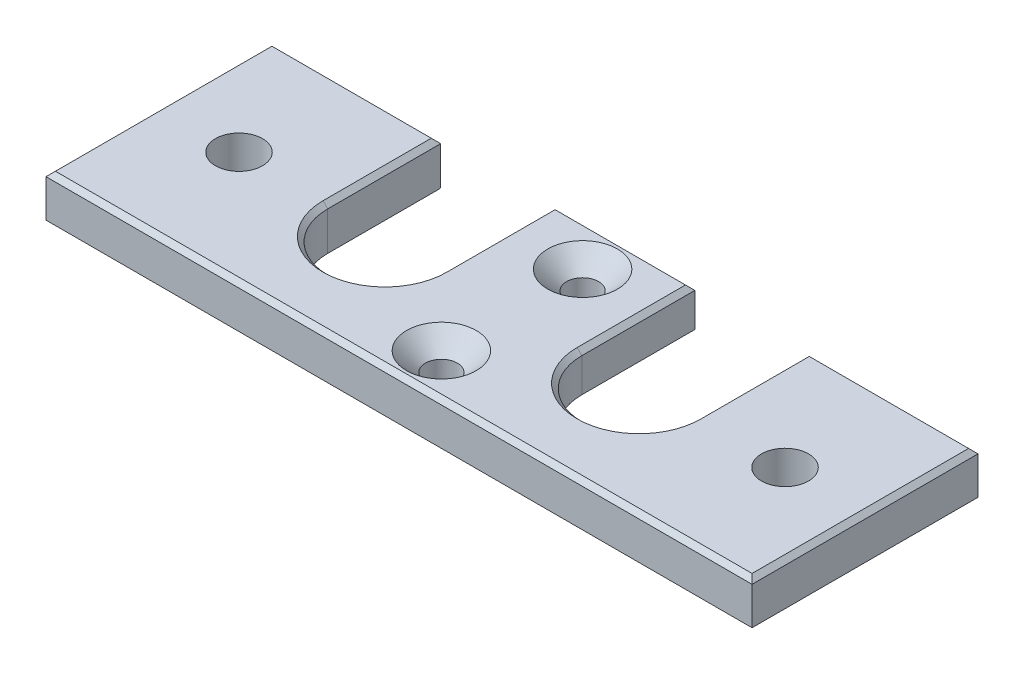
SolidWorks part; units mm, degrees
ref_plane "Front Plane" through (0, 0, 0) normal (0, 0, 1) x (1, 0, 0)
ref_plane "Top Plane" through (0, 0, 0) normal (0, 1, 0) x (1, 0, 0)
ref_plane "Right Plane" through (0, 0, 0) normal (1, 0, 0) x (0, 0, -1)
sketch "Sketch1" plane through (0, 0, 0) normal (0, 1, 0) x (1, 0, 0)
  line L0 (0, 0) -> (0, 50000) construction
  line L1 (37.5, -12) -> (-37.5, -12)
  line L2 (37.5, -12) -> (37.5, 12)
  line L3 (37.5, 12) -> (-37.5, 12)
  line L4 (-37.5, -12) -> (-37.5, 12)
  line L5 (37.5, -12) -> (-37.5, 12) construction
  line L6 (37.5, 12) -> (-37.5, -12) construction
  line L7 (0, 0) -> (50000, 0) construction
  line L8 (-19.575, 0) -> (-19.575, 12)
  line L9 (-7.425, 0) -> (-7.425, 12)
  line L10 (7.425, 0) -> (7.425, 12)
  line L11 (19.575, 0) -> (19.575, 12)
  circle A0 centre (-29, 0) radius 2.5
  circle A1 centre (-13.5, 0) radius 6.075
  circle A2 centre (29, 0) radius 2.5
  circle A3 centre (13.5, 0) radius 6.075
  circle A4 centre (0, -7.5) radius 1.7
  circle A5 centre (0, 7.5) radius 1.7
  point P0 (0, 0)
  dimension "D3" = 27
  dimension "D5" = 5
  dimension "D6" = 12.15
  dimension "D7" = 3.4
  dimension "D1" = 24
  dimension "D2" = 75
  dimension "D4" = 58
  dimension "D8" = 7.5
  dimension "D9" = 7.5
extrude "Boss-Extrude1" add sketch "Sketch1" along normal blind 5 contours L11 A3 L10 L3 L9 A1 L8 L4 L1 L2 A2 A0 region at (0, 0, 1.0866)
chamfer "Chamfer2" distance 2 angle 45 2 edges at (0, 5, -5.8) (0, 5, 9.2)
sketch "Sketch2" plane through (0, 0, 0) normal (0, -1, 0) x (1, 0, 0)
  line L9 (-5.025, 0) -> (-5.025, -12)
  line L10 (-21.975, -12) -> (-21.975, 0)
  line L11 (-5.025, 0) -> (-5.025, -12)
  line L12 (-21.975, -12) -> (-21.975, 0)
  line L14 (21.975, -12) -> (5.025, -12)
  line L15 (-5.025, -12) -> (-21.975, -12)
  line L16 (21.975, 0) -> (21.975, -12)
  line L17 (5.025, -12) -> (5.025, 0)
  line L18 (21.975, 0) -> (21.975, -12)
  line L19 (5.025, -12) -> (5.025, 0)
  arc A7 (-5.025, 0) -> (-21.975, 0) centre (-13.5, 0) ccw
  arc A8 (-5.025, 0) -> (-21.975, 0) centre (-13.5, 0) ccw
  arc A12 (21.975, 0) -> (5.025, 0) centre (13.5, 0) ccw
  arc A13 (21.975, 0) -> (5.025, 0) centre (13.5, 0) ccw
  dimension "D1" = 2.4
  dimension "D2" = 2.4
extrude "Cut-Extrude1" cut sketch "Sketch2" against normal blind 0.4
chamfer "Chamfer1" distance 0.5 angle 45 21 edges at (28.5375, 5, -12) (37.5, 5, 0) (0, 5, 12) (-37.5, 5, 0) (-28.5375, 5, -12) (-19.575, 5, -6) (-13.5, 5, 6.075) (-7.425, 5, -6) (0, 5, -12) (7.425, 5, -6) (13.5, 5, 6.075) (19.575, 5, -6) (29.7375, 0, -12) (37.5, 0, 0) (0, 0, 12) (-37.5, 0, 0) (-29.7375, 0, -12) (0, 0, -12) (7.425, 0.4, -6) (19.575, 0.4, -6) (13.5, 0.4, 6.075)
